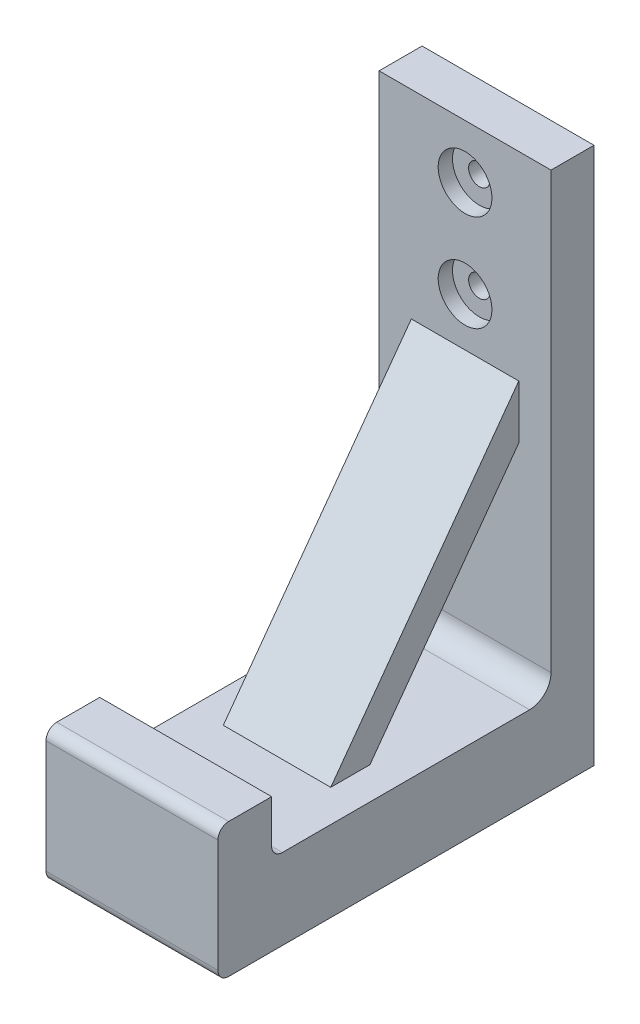
SolidWorks part; units mm, degrees
ref_plane "Front Plane" through (0, 0, 0) normal (0, 0, 1) x (1, 0, 0)
ref_plane "Top Plane" through (0, 0, 0) normal (0, 1, 0) x (1, 0, 0)
ref_plane "Right Plane" through (0, 0, 0) normal (1, 0, 0) x (0, 0, -1)
sketch "Sketch1" plane through (0, 0, 0) normal (1, 0, 0) x (0, 0, -1)
  line L0 (0, 0) -> (0, 127)
  line L5 (0, 127) -> (-10.16, 127)
  line L6 (-10.16, 127) -> (-10.16, 19.05)
  line L11 (-10.16, 19.05) -> (-76.2, 19.05)
  line L12 (-76.2, 19.05) -> (-76.2, 31.75)
  line L13 (-76.2, 31.75) -> (-88.9, 31.75)
  line L14 (-88.9, 31.75) -> (-88.9, 0)
  line L15 (-88.9, 0) -> (0, 0)
  line L16 (-54.61, 19.05) -> (-10.16, 80.01)
  line L17 (-45.3496, 19.05) -> (-10.16, 67.31)
  line L18 (-54.61, 19.05) -> (-45.3496, 19.05)
  line L19 (-10.16, 67.31) -> (-10.16, 80.01)
  dimension "D1" = 127
  dimension "D2" = 88.9
  dimension "D3" = 10.16
  dimension "D4" = 12.7
  dimension "D5" = 19.05
  dimension "D6" = 12.7
  dimension "D7" = 44.45
  dimension "D8" = 60.96
  dimension "D10" = 12.7
extrude "Boss-Extrude1" add sketch "Sketch1" along normal mid plane 40.64 contours L0 L5 L6 L11 L12 L13 L14 L15
extrude "Boss-Extrude2" add sketch "Sketch1<9>" along normal mid plane 25.4 contours L16 L19 L17 L18
sketch "Sketch1<9>" plane through (0, 0, 0) normal (1, 0, 0) x (0, 0, -1) same geometry as "Sketch1"
hole_wizard "CBORE for #10 Pan Head Machine Screw1" positions "Sketch2" profile "Sketch3" counterbore size "#10" standard "ANSI Inch" end condition through all
sketch "Sketch2" plane through (0, 0, 10.16) normal (0, 0, 1) x (1, 0, 0)
  line L0 (-20.32, 127) -> (-20.32, 19.05) construction
  line L1 (20.32, 127) -> (-20.32, 127) construction
  point P0 (0, 91.44)
  point P2 (0, 114.3)
  dimension "D1" = 20.32
  dimension "D2" = 20.32
  dimension "D3" = 12.7
  dimension "D4" = 35.56
sketch "Sketch3" plane through (0, 91.44, 10.16) normal (1, 0, 0) x (0, -1, 0)
  line L0 (0, 0) -> (0, 10.16)
  line L1 (0, 10.16) -> (2.54, 10.16)
  line L3 (2.54, 10.16) -> (2.54, 3.3782)
  line L4 (2.54, 3.3782) -> (6.35, 3.3782)
  line L5 (6.35, 3.3782) -> (6.35, 0)
  line L7 (6.35, 0) -> (0, 0)
  line L11 (0, -6.35) -> (0, 107.95) construction
  dimension "Thru Hole Dia." = 5.08
  dimension "Thru Hole Depth" = 10.16
  dimension "C'Bore Dia." = 12.7
  dimension "C'Bore Depth" = 3.3782
fillet "Fillet1" radius 5.08 1 edges at (0, 19.05, 10.16)
fillet "Fillet2" radius 2.54 1 edges at (0, 19.05, 76.2)
fillet "Fillet3" radius 2.54 1 edges at (0, 0, 88.9)
fillet "Fillet4" radius 2.54 1 edges at (0, 31.75, 88.9)
